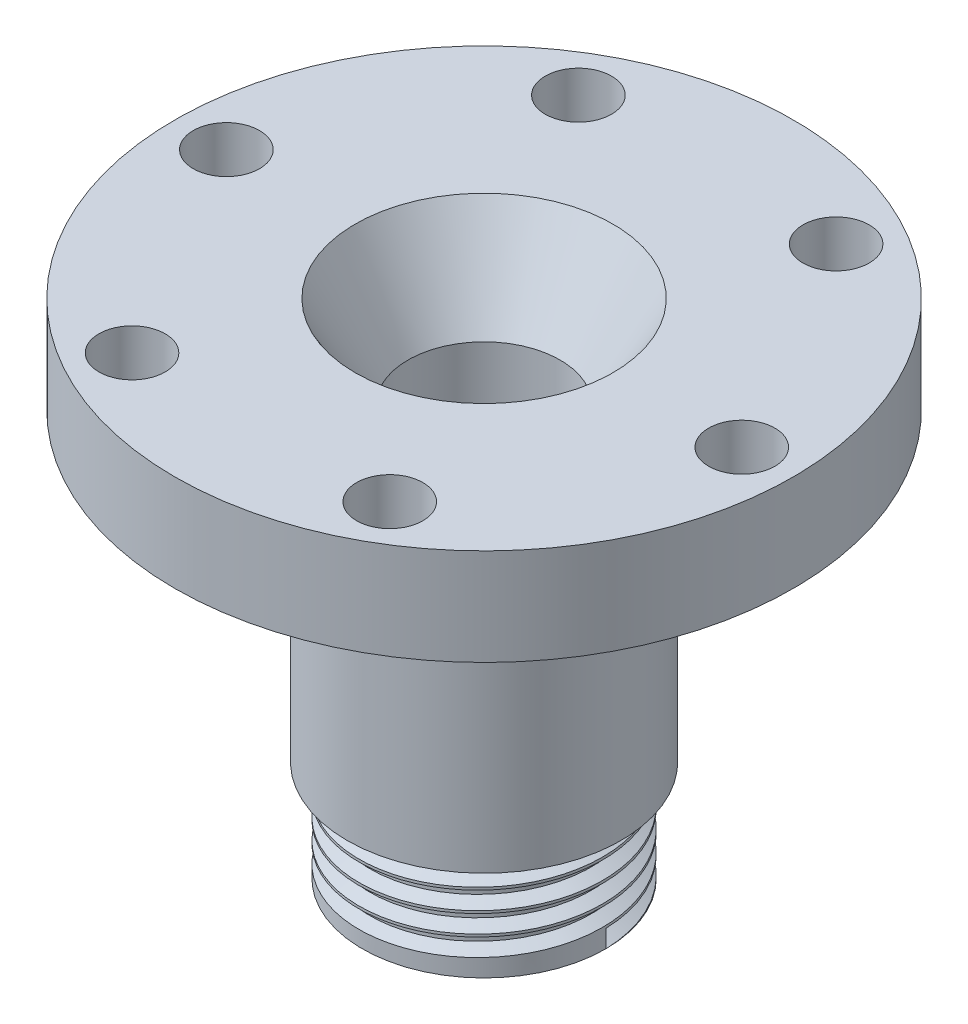
SolidWorks part; units mm, degrees
material "AISI Type 316L stainless steel"
ref_plane "Front Plane" through (0, 0, 0) normal (0, 0, 1) x (1, 0, 0)
ref_plane "Top Plane" through (0, 0, 0) normal (0, 1, 0) x (1, 0, 0)
ref_plane "Right Plane" through (0, 0, 0) normal (1, 0, 0) x (0, 0, -1)
sketch "Sketch1" plane through (0, 0, 0) normal (0, 0, 1) x (1, 0, 0)
  line L0 (0, 0) -> (0, -29.8554) construction
  line L1 (7.5, -49.525) -> (7.5, -9.0067)
  line L2 (7.5, -9.0067) -> (12.7, 0)
  line L3 (12.7, 0) -> (30.48, 0)
  line L4 (30.48, 0) -> (30.48, -9.525)
  line L5 (30.48, -9.525) -> (13.5, -9.525)
  line L6 (13.5, -9.525) -> (13.5, -49.525)
  line L7 (13.5, -49.525) -> (7.5, -49.525)
  dimension "D1" = 27
  dimension "D2" = 15
  dimension "D3" = 40
  dimension "D4" = 30
  dimension "D5" = 25.4
  dimension "D6" = 60.96
  dimension "D7" = 9.525
revolve "Revolve1" add sketch "Sketch1" angle 360 about L0
hole_wizard "1/4 Clearance Hole1" positions "Sketch3" profile "Sketch4" hole size "1/4" standard "ANSI Inch" end condition through all
sketch "Sketch3" plane through (0, 0, 0) normal (0, 1, 0) x (1, 0, 0)
  line L0 (25.4, 0) -> (0, 0) construction
  point P0 (25.4, 0)
  dimension "D1" = 25.4
sketch "Sketch4" plane through (25.4, 0, 0) normal (1, 0, 0) x (0, 0, 1)
  line L0 (0, 0) -> (0, 49.525)
  line L1 (0, 49.525) -> (3.2639, 49.525)
  line L2 (3.2639, 49.525) -> (3.2639, 0)
  line L5 (3.2639, 0) -> (0, 0)
  line L11 (0, -6.35) -> (0, 107.95) construction
  dimension "Thru Hole Dia." = 6.5278
  dimension "Thru Hole Depth" = 49.525
pattern_circular "CirPattern1" count 6 over 360 about axis through (0, 0, 0) along (0, 1, 0) of "1/4 Clearance Hole1" reverse direction yes
sketch "Sketch5" plane through (0, 0, 0) normal (0, 1, 0) x (1, 0, 0)
  circle A0 centre (0, 0) radius 25.4
  dimension "D1" = 50.8
chamfer "Chamfer2" distance 3.175 angle 45 1 edges at (0, -9.525, 13.5)
ref_plane "Plane1" through (0, -49.525, 0) normal (0, -1, 0) x (-1, 0, 0)
sketch "Sketch6" plane through (0, -49.525, 0) normal (0, -1, 0) x (-1, 0, 0)
  circle A0 centre (0, 0) radius 14.1665
  circle A1 centre (0, 0) radius 12
  dimension "D1" = 28.3329
  dimension "D2" = 24
extrude "Cut-Extrude1" cut sketch "Sketch6" against normal blind 10
thread "Thread1" pitch 2 method cut profile "Thread Profile2" start angle 0, offset 0, length 10, pitch 2, diameter 24
ref_plane "Plane3" through (12, -49.525, 0) normal (0, 0, 1) x (1, 0, 0)
sketch "Thread Profile2" plane through (12, -49.525, 0) normal (0, 0, 1) x (1, 0, 0)
  line L0 (0, 0) -> (0, 2) construction
  line L11 (0, 0) -> (0, 1.75)
  line L12 (0, 1.75) -> (-1.0825, 1.125)
  line L13 (-1.0825, 1.125) -> (-1.0825, 0.625)
  line L15 (-1.0825, 0.625) -> (0, 0)
  line L17 (-1.0825, 0.875) -> (0, 0.875) construction
  point P2 (0, 0)
  dimension "Pitch" = 2
  dimension "Profile_Angle" = 60
  dimension "Profile_Land" = 0.5
  dimension "Profile_Height" = 1.0825
